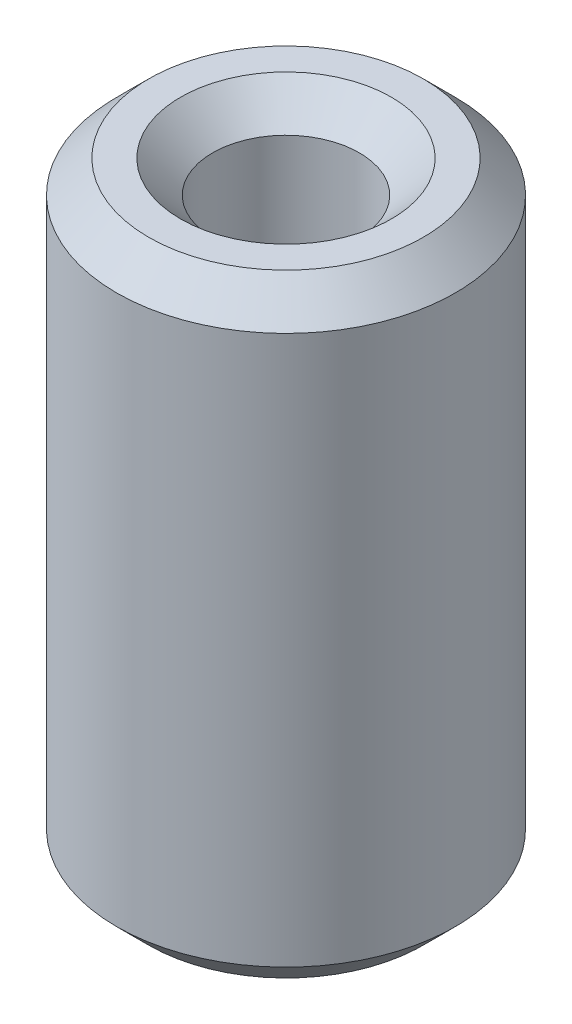
SolidWorks part; units mm, degrees
ref_plane "Front Plane" through (0, 0, 0) normal (0, 0, 1) x (1, 0, 0)
ref_plane "Top Plane" through (0, 0, 0) normal (0, 1, 0) x (1, 0, 0)
ref_plane "Right Plane" through (0, 0, 0) normal (1, 0, 0) x (0, 0, -1)
sketch "Sketch1" plane through (0, 0, 0) normal (0, 1, 0) x (1, 0, 0)
  circle A0 centre (0, 0) radius 17.5
  dimension "SLEEVE_OD" = 35
extrude "Boss-Extrude1" add sketch "Sketch1" along normal blind 63.3335
sketch "Sketch2" plane through (0, 0, 0) normal (0, 1, 0) x (1, 0, 0)
  circle A0 centre (0, 0) radius 7.5809
  dimension "BORE_D" = 15.1619
extrude "Cut-Extrude1" cut sketch "Sketch2" along normal through all
chamfer "Chamfer1" distance 3.3163 angle 45 4 edges at (0, 63.3335, 7.5809) (0, 0, 7.5809) (0, 0, 17.5) (0, 63.3335, 17.5)
